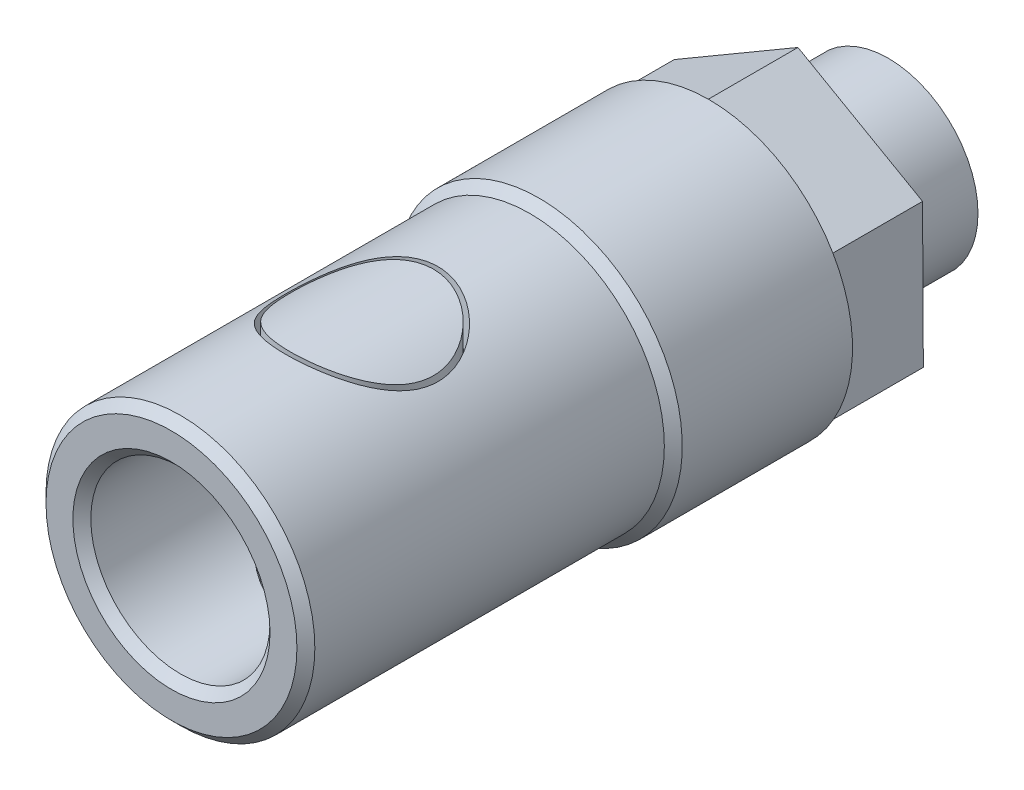
SolidWorks part; units mm, degrees
ref_plane "Front" through (0, 0, 0) normal (0, 0, 1) x (1, 0, 0)
ref_plane "Top" through (0, 0, 0) normal (0, 1, 0) x (1, 0, 0)
ref_plane "Right" through (0, 0, 0) normal (1, 0, 0) x (0, 0, -1)
sketch "Sketch1" plane through (0, 0, 0) normal (0, 0, 1) x (1, 0, 0)
  circle A0 centre (0, 0) radius 15
  circle A1 centre (0, 0) radius 10
  dimension "D1" = 30
  dimension "D2" = 20
extrude "Boss-Extrude1" add sketch "Sketch1" along normal blind 40
sketch "Sketch2" plane through (0, 0, 0) normal (0, 0, -1) x (-1, 0, 0)
  circle A0 centre (0, 0) radius 16
  dimension "D1" = 32
extrude "Extrude-Thin1" add sketch "Sketch2" along normal blind 20 thin thin type one direction reverse wall 10
chamfer "Chamfer1" distance 1 angle 45 1 edges at (-16, 0, 0)
chamfer "Chamfer2" distance 1 angle 45 2 edges at (10, 0, 40) (15, 0, 40)
sketch "Sketch3" plane through (0, 0, -20) normal (0, 0, -1) x (-1, 0, 0)
  line L1 (13.9006, 7.9229) -> (0.0889, 15.9998)
  line L2 (0.0889, 15.9998) -> (-13.8118, 8.0768)
  line L3 (-13.8118, 8.0768) -> (-13.9006, -7.9229)
  line L4 (-13.9006, -7.9229) -> (-0.0889, -15.9998)
  line L5 (-0.0889, -15.9998) -> (13.8118, -8.0768)
  line L6 (13.8118, -8.0768) -> (13.9006, 7.9229)
  circle A0 centre (0, 0) radius 13.8564 construction
  circle A1 centre (0, 0) radius 6
extrude "Boss-Extrude2" add sketch "Sketch3" along normal blind 10
sketch "Sketch4" plane through (0, 0, -30) normal (0, 0, -1) x (-1, 0, 0)
  circle A0 centre (0, 0) radius 10
  circle A1 centre (0, 0) radius 6
  dimension "D1" = 20
extrude "Boss-Extrude3" add sketch "Sketch4" along normal blind 10
sketch "Sketch6" plane through (0, 0, 0) normal (0, 1, 0) x (1, 0, 0)
  circle A0 centre (0, -18.7491) radius 8.493
  circle A1 centre (0, -18.7491) radius 7.993
  dimension "D1" = 0.5
extrude "Cut-Extrude1" cut sketch "Sketch6" against normal through all both and the other way through all
